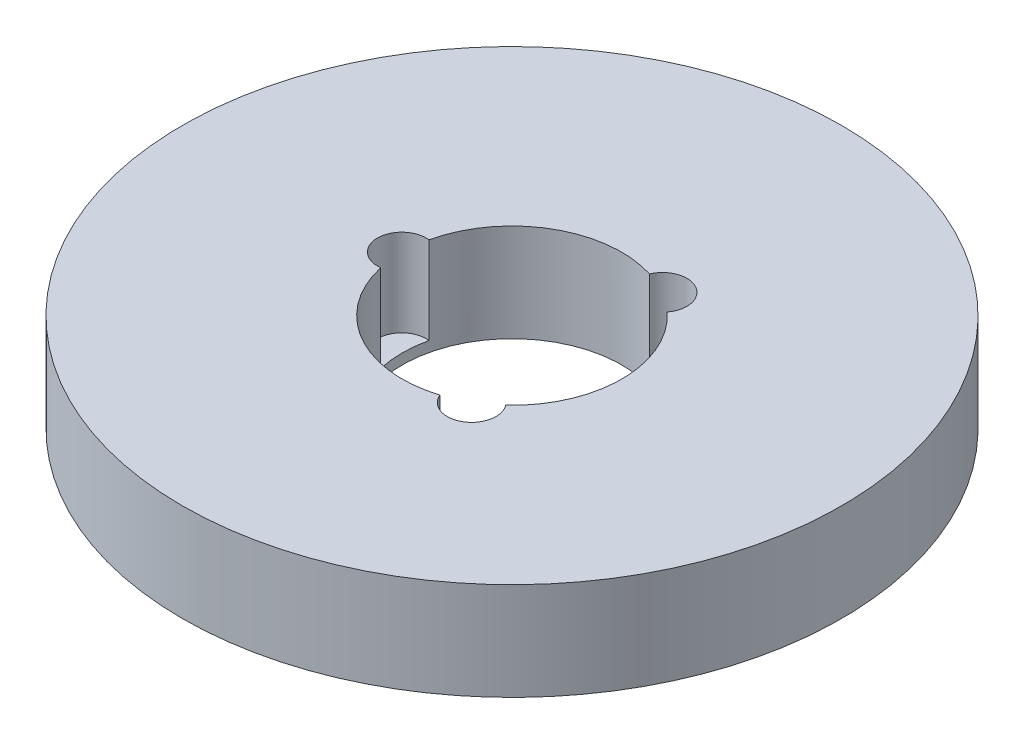
SolidWorks part; units mm, degrees
ref_plane "Front Plane" through (0, 0, 0) normal (0, 0, 1) x (1, 0, 0)
ref_plane "Top Plane" through (0, 0, 0) normal (0, 1, 0) x (1, 0, 0)
ref_plane "Right Plane" through (0, 0, 0) normal (1, 0, 0) x (0, 0, -1)
sketch "Sketch1" plane through (0, 0, 0) normal (0, 1, 0) x (1, 0, 0)
  circle A0 centre (0, 0) radius 67.5
  dimension "FLANGE_OD" = 135
extrude "Boss-Extrude1" add sketch "Sketch1" along normal blind 20
sketch "Sketch2" plane through (0, 0, 0) normal (0, 1, 0) x (1, 0, 0)
  circle A0 centre (0, 0) radius 22.5
  dimension "BORE_D" = 45
extrude "Cut-Extrude1" cut sketch "Sketch2" along normal through all
sketch "Sketch3" plane through (0, 20, 0) normal (0, 1, 0) x (1, 0, 0)
  circle A0 centre (0, 0) radius 22.5721 construction
  circle A1 centre (-22.5721, 0) radius 4.983
  dimension "BOLT_D" = 9.966
  dimension "BOLT_PCD" = 45.1442
extrude "Cut-Extrude2" cut sketch "Sketch3" against normal blind 17.8654
pattern_circular "CirPattern1" count 3 over 360 about axis through (0, 0, 0) along (0, 1, 0) of "Cut-Extrude2"
